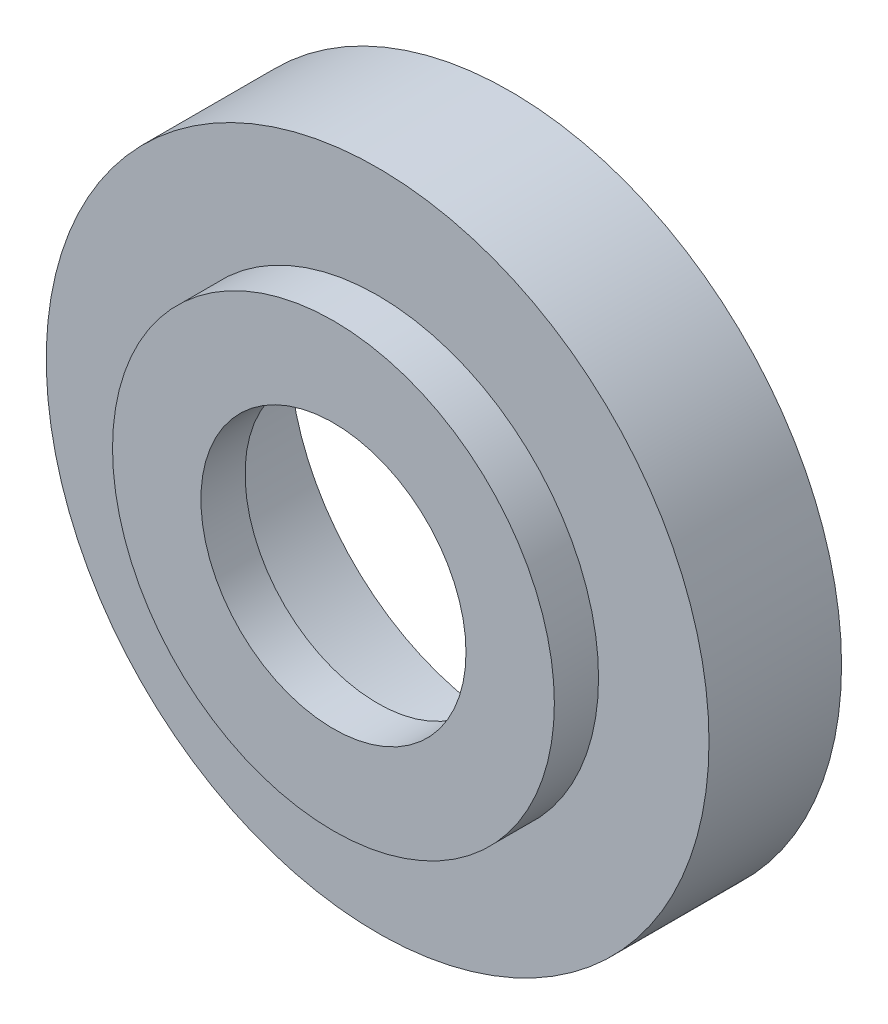
SolidWorks part; units mm, degrees
ref_plane "Front Plane" through (0, 0, 0) normal (0, 0, 1) x (1, 0, 0)
ref_plane "Top Plane" through (0, 0, 0) normal (0, 1, 0) x (1, 0, 0)
ref_plane "Right Plane" through (0, 0, 0) normal (1, 0, 0) x (0, 0, -1)
sketch "Sketch1" plane through (0, 0, 0) normal (0, 0, 1) x (1, 0, 0)
  circle A0 centre (0, 0) radius 1.5
  circle A1 centre (0, 0) radius 2.5
  circle A2 centre (0, 0) radius 3.75
  dimension "D1" = 3
  dimension "D2" = 5
  dimension "D3" = 7.5
extrude "Boss-Extrude1" add sketch "Sketch1" along normal blind 1.5 contours A2 A1 region at (-3.6439, 0, 0)
extrude "Boss-Extrude2" add sketch "Sketch1<3>" along normal blind 0.5 from surface separate body contours A1 A0 region at (-2.4293, 0, 0) starting at face at (2.5, 0, 1.5)
sketch "Sketch1<3>" plane through (0, 0, 0) normal (0, 0, 1) x (1, 0, 0) same geometry as "Sketch1"
